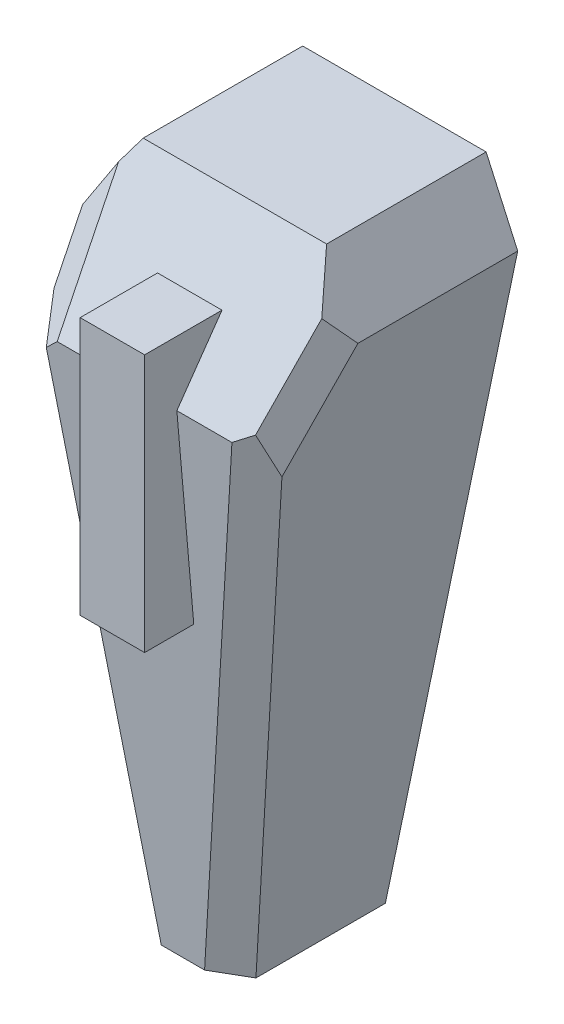
SolidWorks part; units mm, degrees
ref_plane "Front Plane" through (0, 0, 0) normal (0, 0, 1) x (1, 0, 0)
ref_plane "Top Plane" through (0, 0, 0) normal (0, 1, 0) x (1, 0, 0)
ref_plane "Right Plane" through (0, 0, 0) normal (1, 0, 0) x (0, 0, -1)
sketch "Sketch1" plane through (0, 0, 0) normal (0, 0, 1) x (1, 0, 0)
  line L1 (0, 0) -> (10.16, 0)
  line L2 (0, 0) -> (0, 25.4)
  line L3 (0, 25.4) -> (10.16, 25.4)
  line L4 (10.16, 0) -> (10.16, 25.4)
  dimension "D1" = 10.16
  dimension "D2" = 25.4
extrude "Boss-Extrude1" add sketch "Sketch1" along normal blind 10.16
chamfer "Chamfer1" distance 5.08 angle 35 1 edges at (5.08, 25.4, 10.16)
chamfer "Chamfer6" distance 22.86 angle 8 1 edges at (0, 0, 5.08)
chamfer "Chamfer7" distance 22.86 angle 8 1 edges at (10.16, 0, 5.08)
chamfer "Chamfer10" distance 2.54 angle 30 1 edges at (0, 25.4, 3.3015)
chamfer "Chamfer11" distance 2.54 angle 30 1 edges at (10.16, 25.4, 3.3015)
sketch "Sketch2" plane through (0, 0, 0) normal (0, 0, -1) x (-1, 0, 0)
  line L0 (-8.6935, 25.4) -> (-1.4665, 25.4)
  line L2 (-5.08, 12.7) -> (-3.81, 12.7)
  line L3 (-3.81, 12.7) -> (-3.81, 22.86)
  line L4 (-5.08, 22.86) -> (-6.35, 22.86)
  line L5 (-6.35, 22.86) -> (-6.35, 12.7)
  line L6 (-6.35, 12.7) -> (-5.08, 12.7)
  line L7 (-5.08, 22.86) -> (-3.81, 22.86)
extrude "Boss-Extrude2" add sketch "Sketch2" against normal blind 11.43 contours L7 L4 L5 L6 L2 L3
chamfer "Chamfer12" distance 20.32 angle 5 1 edges at (5.08, 0, 10.16)
chamfer "Chamfer13" distance 1.27 angle 30 2 edges at (0.1785, 21.59, 9.2707) (1.7849, 10.16, 9.2711)
chamfer "Chamfer14" distance 1.27 angle 30 2 edges at (9.9815, 21.59, 9.2707) (8.3751, 10.16, 9.2711)
chamfer "Chamfer15" distance 2.54 angle 85 1 edges at (5.08, 0, 0)
scale "Scale1" scale about centroid uniform scaling yes scale factor 1.5
sketch "Sketch5" plane through (0, 0.0417, 0.4766) normal (0, -0.0872, -0.9962) x (-1, 0, 0)
  line L0 (-5.0794, 30.5974) -> (-5.0794, 26.7874)
  line L1 (-10.4997, 30.5974) -> (0.3409, 30.5974) construction
  line L2 (-5.0794, 26.7874) -> (-2.1276, 26.7874)
  line L3 (-2.1276, 26.7874) -> (-2.1276, 17.6988)
  line L4 (-2.1276, 17.6988) -> (-8.0311, 17.6988)
  line L5 (-8.0311, 17.6988) -> (-8.0311, 26.7874)
  line L6 (-8.0311, 26.7874) -> (-5.0794, 26.7874)
extrude "Boss-Extrude4" add sketch "Sketch5" along normal blind 0.254 contours L6 L5 L4 L3 L2
